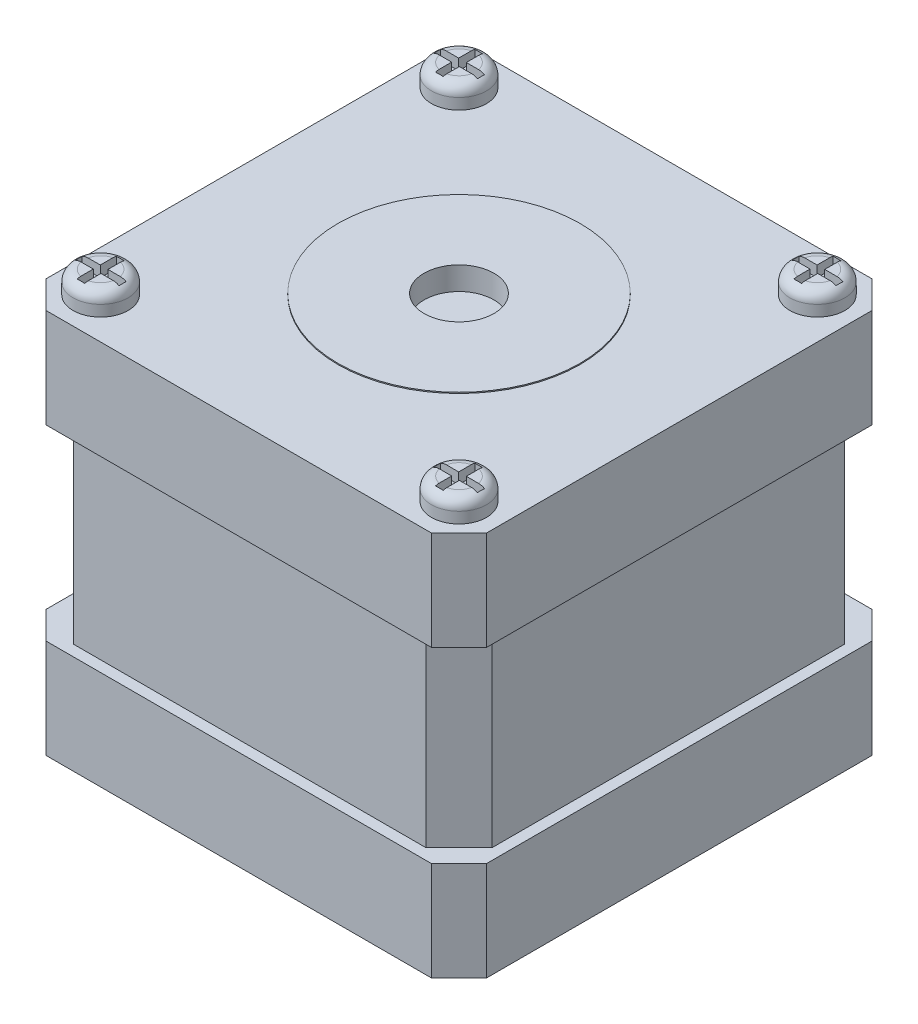
SolidWorks part; units mm, degrees
ref_plane "Alzado" through (0, 0, 0) normal (0, 0, 1) x (1, 0, 0)
ref_plane "Planta" through (0, 0, 0) normal (0, 1, 0) x (1, 0, 0)
ref_plane "Vista lateral" through (0, 0, 0) normal (1, 0, 0) x (0, 0, -1)
sketch "Croquis1" plane through (0, 0, 0) normal (0, 1, 0) x (1, 0, 0)
  line L1 (-20, -20) -> (20, -20)
  line L2 (-20, -20) -> (-20, 20)
  line L3 (-20, 20) -> (20, 20)
  line L4 (20, -20) -> (20, 20)
  line L5 (-20, -20) -> (20, 20) construction
  line L6 (-20, 20) -> (20, -20) construction
  point P0 (0, 0)
  dimension "D1" = 40
  dimension "D2" = 40
extrude "Saliente-Extruir1" add sketch "Croquis1" along normal blind 9
sketch "Croquis2" plane through (0, 9, 0) normal (0, 1, 0) x (1, 0, 0)
  line L0 (-20, 0) -> (0, 0) construction
  line L1 (-20, 20) -> (-20, -20) construction
  line L3 (19, -19) -> (-19, -19)
  line L4 (19, -19) -> (19, 19)
  line L5 (19, 19) -> (-19, 19)
  line L6 (-19, -19) -> (-19, 19)
  line L7 (19, -19) -> (-19, 19) construction
  line L8 (19, 19) -> (-19, -19) construction
  dimension "D1" = 38
  dimension "D2" = 38
extrude "Saliente-Extruir2" add sketch "Croquis2" along normal blind 17
sketch "Croquis3" plane through (0, 26, 0) normal (0, 1, 0) x (1, 0, 0)
  line L1 (-20, -20) -> (20, -20)
  line L2 (-20, -20) -> (-20, 20)
  line L3 (-20, 20) -> (20, 20)
  line L4 (20, -20) -> (20, 20)
extrude "Saliente-Extruir3" add sketch "Croquis3" along normal blind 9
chamfer "Chaflán1" distance 3 angle 45 4 edges at (-19, 17.5, -19) (19, 17.5, -19) (-19, 17.5, 19) (19, 17.5, 19)
chamfer "Chaflán2" distance 2.5 angle 45 8 edges at (-20, 4.5, 20) (20, 4.5, 20) (20, 30.5, 20) (-20, 30.5, 20) (20, 4.5, -20) (-20, 4.5, -20) (20, 30.5, -20) (-20, 30.5, -20)
sketch "Croquis4" plane through (0, 35, 0) normal (0, 1, 0) x (1, 0, 0)
  line L0 (20, 0) -> (-20, 0) construction
  line L1 (20, -17.5) -> (20, 17.5) construction
  line L2 (-20, 17.5) -> (-20, -17.5) construction
  circle A0 centre (0, 0) radius 3.175
  dimension "D1" = 6.35
extrude "Cortar-Extruir1" cut sketch "Croquis4" against normal blind 2
sketch "Croquis5" plane through (0, 35, 0) normal (0, 1, 0) x (1, 0, 0)
  circle A0 centre (0, 0) radius 11
  circle A1 centre (0, 0) radius 3.175
  dimension "D1" = 22
extrude "Saliente-Extruir4" add sketch "Croquis5" along normal blind 0.1
sketch "Croquis6" plane through (0, 35, 0) normal (0, 1, 0) x (1, 0, 0)
  line L0 (-18.75, -18.75) -> (-16.2751, -16.2751) construction
  line L1 (-20, -17.5) -> (-17.5, -20) construction
  line L2 (-20, 0) -> (0, 0) construction
  line L3 (-20, 17.5) -> (-20, -17.5) construction
  line L4 (-18.75, 18.75) -> (-16.2751, 16.2751) construction
  line L5 (0, -20) -> (0, 0) construction
  line L6 (-17.5, -20) -> (17.5, -20) construction
  line L7 (18.75, 18.75) -> (16.2751, 16.2751) construction
  line L8 (18.75, -18.75) -> (16.2751, -16.2751) construction
  circle A0 centre (-16.2751, -16.2751) radius 2.5
  circle A1 centre (-16.2751, 16.2751) radius 2.5
  circle A2 centre (16.2751, 16.2751) radius 2.5
  circle A3 centre (16.2751, -16.2751) radius 2.5
  dimension "D2" = 5
  dimension "D1" = 3.5
extrude "Saliente-Extruir5" add sketch "Croquis6" along normal blind 2
sketch "Croquis7" plane through (0, 37, 0) normal (0, 1, 0) x (1, 0, 0)
  line L0 (-15.927, -15.9564) -> (-15.927, -14.4902)
  line L1 (-14.28, -16.5938) -> (-15.927, -16.5938)
  line L2 (-14.28, -16.5938) -> (-14.28, -15.9564)
  line L3 (-14.28, -15.9564) -> (-15.927, -15.9564)
  line L4 (-18.2703, -16.5938) -> (-18.2703, -15.9564)
  line L5 (-14.28, -16.5938) -> (-18.2703, -15.9564) construction
  line L6 (-14.28, -15.9564) -> (-18.2703, -16.5938) construction
  line L7 (-15.927, -18.0601) -> (-16.6233, -18.0601)
  line L8 (-15.927, -18.0601) -> (-15.927, -16.5938)
  line L9 (-15.927, -14.4902) -> (-16.6233, -14.4902)
  line L10 (-16.6233, -18.0601) -> (-16.6233, -16.5938)
  line L11 (-15.927, -18.0601) -> (-16.6233, -14.4902) construction
  line L12 (-15.927, -14.4902) -> (-16.6233, -18.0601) construction
  line L13 (-16.6233, -16.5938) -> (-18.2703, -16.5938)
  line L14 (-16.6233, -15.9564) -> (-16.6233, -14.4902)
  line L15 (-16.6233, -15.9564) -> (-18.2703, -15.9564)
  line L16 (-20, 0) -> (0, 0) construction
  line L17 (-20, 17.5) -> (-20, -17.5) construction
  line L18 (-15.927, 14.4902) -> (-16.6233, 18.0601) construction
  line L19 (-15.927, 18.0601) -> (-16.6233, 14.4902) construction
  line L20 (-14.28, 15.9564) -> (-18.2703, 16.5938) construction
  line L21 (-14.28, 16.5938) -> (-18.2703, 15.9564) construction
  line L22 (-16.6233, 15.9564) -> (-18.2703, 15.9564)
  line L23 (-16.6233, 15.9564) -> (-16.6233, 14.4902)
  line L24 (-16.6233, 16.5938) -> (-18.2703, 16.5938)
  line L25 (-16.6233, 18.0601) -> (-16.6233, 16.5938)
  line L26 (-15.927, 14.4902) -> (-16.6233, 14.4902)
  line L27 (-15.927, 18.0601) -> (-15.927, 16.5938)
  line L28 (-15.927, 18.0601) -> (-16.6233, 18.0601)
  line L29 (-18.2703, 16.5938) -> (-18.2703, 15.9564)
  line L30 (-14.28, 15.9564) -> (-15.927, 15.9564)
  line L31 (-14.28, 16.5938) -> (-14.28, 15.9564)
  line L32 (-14.28, 16.5938) -> (-15.927, 16.5938)
  line L33 (-15.927, 15.9564) -> (-15.927, 14.4902)
  line L34 (0, 0) -> (0, 20) construction
  line L35 (17.5, 20) -> (-17.5, 20) construction
  line L36 (14.28, 16.5938) -> (18.2703, 15.9564) construction
  line L37 (14.28, 15.9564) -> (18.2703, 16.5938) construction
  line L38 (15.927, 18.0601) -> (16.6233, 14.4902) construction
  line L39 (15.927, 14.4902) -> (16.6233, 18.0601) construction
  line L40 (15.927, -14.4902) -> (16.6233, -18.0601) construction
  line L41 (15.927, -18.0601) -> (16.6233, -14.4902) construction
  line L42 (14.28, -15.9564) -> (18.2703, -16.5938) construction
  line L43 (14.28, -16.5938) -> (18.2703, -15.9564) construction
  line L44 (15.927, 15.9564) -> (15.927, 14.4902)
  line L45 (14.28, 16.5938) -> (15.927, 16.5938)
  line L46 (14.28, 16.5938) -> (14.28, 15.9564)
  line L47 (14.28, 15.9564) -> (15.927, 15.9564)
  line L48 (18.2703, 16.5938) -> (18.2703, 15.9564)
  line L49 (15.927, 18.0601) -> (16.6233, 18.0601)
  line L50 (15.927, 18.0601) -> (15.927, 16.5938)
  line L51 (15.927, 14.4902) -> (16.6233, 14.4902)
  line L52 (16.6233, 18.0601) -> (16.6233, 16.5938)
  line L53 (16.6233, 16.5938) -> (18.2703, 16.5938)
  line L54 (16.6233, 15.9564) -> (16.6233, 14.4902)
  line L55 (16.6233, 15.9564) -> (18.2703, 15.9564)
  line L56 (16.6233, -15.9564) -> (18.2703, -15.9564)
  line L57 (16.6233, -15.9564) -> (16.6233, -14.4902)
  line L58 (16.6233, -16.5938) -> (18.2703, -16.5938)
  line L59 (16.6233, -18.0601) -> (16.6233, -16.5938)
  line L60 (15.927, -14.4902) -> (16.6233, -14.4902)
  line L61 (15.927, -18.0601) -> (15.927, -16.5938)
  line L62 (15.927, -18.0601) -> (16.6233, -18.0601)
  line L63 (18.2703, -16.5938) -> (18.2703, -15.9564)
  line L64 (14.28, -15.9564) -> (15.927, -15.9564)
  line L65 (14.28, -16.5938) -> (14.28, -15.9564)
  line L66 (14.28, -16.5938) -> (15.927, -16.5938)
  line L67 (15.927, -15.9564) -> (15.927, -14.4902)
  point P0 (-16.2751, -16.2751)
  point P6 (-16.2751, -16.2751)
  point P32 (-16.2751, 16.2751)
  point P60 (16.2751, 16.2751)
  point P61 (16.2751, -16.2751)
extrude "Cortar-Extruir2" cut sketch "Croquis7" against normal blind 1
fillet "Redondeo1" radius 1 4 edges at (16.2751, 37, -13.7751) (16.2751, 37, 13.7751) (-16.2751, 37, -18.7751) (-16.2751, 37, 18.7751)
